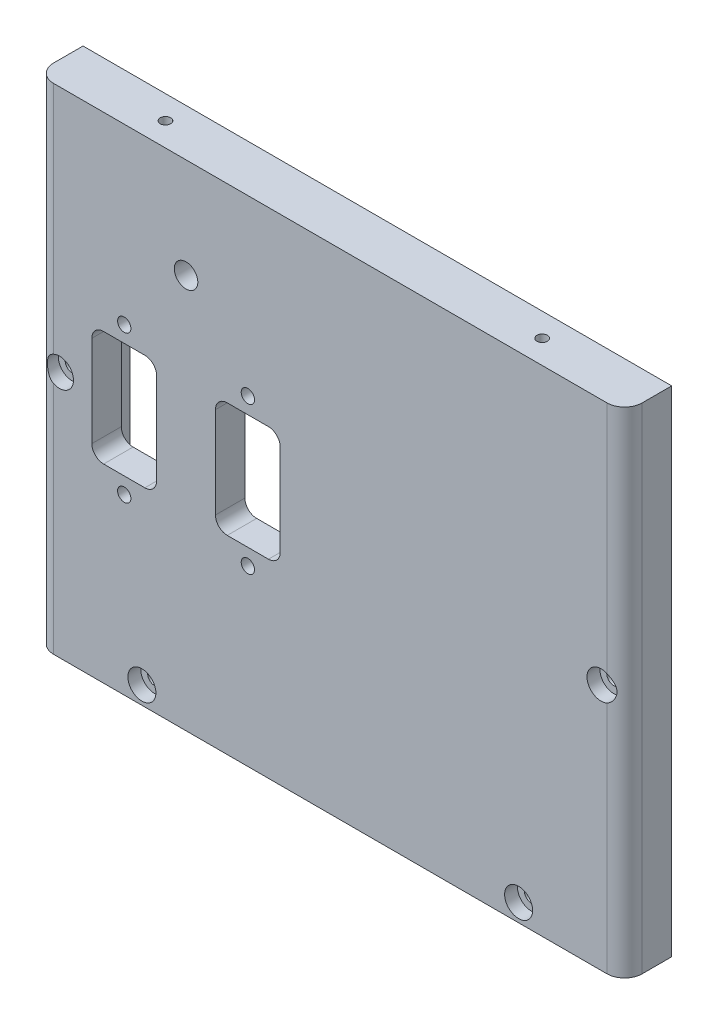
SolidWorks part; units mm, degrees
ref_plane "Front Plane" through (0, 0, 0) normal (0, 0, 1) x (1, 0, 0)
ref_plane "Top Plane" through (0, 0, 0) normal (0, 1, 0) x (1, 0, 0)
ref_plane "Right Plane" through (0, 0, 0) normal (1, 0, 0) x (0, 0, -1)
sketch "Sketch1" plane through (0, 0, 0) normal (0, 0, 1) x (1, 0, 0)
  line L1 (-50, 42) -> (50, 42)
  line L2 (-50, 42) -> (-50, -42)
  line L3 (-50, -42) -> (50, -42)
  line L4 (50, 42) -> (50, -42)
  line L5 (-50, 42) -> (50, -42) construction
  line L6 (-50, -42) -> (50, 42) construction
  point P0 (0, 0)
extrude "Boss-Extrude1" add sketch "Sketch1" along normal blind 8
sketch "Sketch2" plane through (0, 0, 8) normal (0, 0, 1) x (1, 0, 0)
  line L0 (-50, -42) -> (-50, -36) construction
  line L1 (-50, -36) -> (50, -36) construction
  line L2 (50, -42) -> (50, 42) construction
  line L3 (50, -36) -> (50, -42) construction
  line L4 (-50, -39) -> (-32, -39) construction
  line L5 (50, -39) -> (32, -39) construction
hole_wizard "CBORE for #2 Socket Head Cap Screw1" positions "3DSketch1" profile "Sketch3" counterbore size "#2" standard "ANSI Inch"
sketch3d "3DSketch1"
  point P0 (-32, -39, 8)
  point P3 (32, -39, 8)
sketch "Sketch3" plane through (-32, -39, 8) normal (1, 0, 0) x (0, -1, 0)
  line L0 (0, 0) -> (0, 13.0026)
  line L1 (0, 13.0026) -> (1.2192, 12.27)
  line L2 (1.2192, 12.27) -> (1.2192, 2.1844)
  line L3 (1.2192, 2.1844) -> (2.3812, 2.1844)
  line L4 (2.3812, 2.1844) -> (2.3812, 0)
  line L5 (2.3812, 0) -> (0, 0)
  line L10 (0, 13.0026) -> (-1.2192, 12.27) construction
  line L11 (0, -6.35) -> (0, 107.95) construction
  dimension "Hole Dia." = 2.4384
  dimension "Hole Depth" = 12.27
  dimension "C'Bore Dia." = 4.7625
  dimension "C'Bore Depth" = 2.1844
  dimension "Drill Angle" = 118
sketch "Sketch4" plane through (0, 0, 8) normal (0, 0, 1) x (1, 0, 0)
  line L0 (-50, -42) -> (-42, -42) construction
  line L1 (-42, -42) -> (-42, 42) construction
  line L2 (50, 42) -> (-50, 42) construction
  line L3 (-42, 42) -> (-50, 42) construction
  line L4 (50, -42) -> (42, -42) construction
  line L5 (42, -42) -> (42, 42) construction
  line L6 (42, 42) -> (50, 42) construction
  line L7 (46, -42) -> (46, 0) construction
  line L8 (-46, -42) -> (-46, 0) construction
hole_wizard "CBORE for #2 Socket Head Cap Screw2" positions "3DSketch2" profile "Sketch5" counterbore size "#2" standard "ANSI Inch"
sketch3d "3DSketch2"
  point P0 (-46, 0, 8)
  point P3 (46, 0, 8)
sketch "Sketch5" plane through (-46, 0, 8) normal (1, 0, 0) x (0, -1, 0)
  line L0 (0, 0) -> (0, 13.0026)
  line L1 (0, 13.0026) -> (1.2192, 12.27)
  line L2 (1.2192, 12.27) -> (1.2192, 2.1844)
  line L3 (1.2192, 2.1844) -> (2.3812, 2.1844)
  line L4 (2.3812, 2.1844) -> (2.3812, 0)
  line L5 (2.3812, 0) -> (0, 0)
  line L10 (0, 13.0026) -> (-1.2192, 12.27) construction
  line L11 (0, -6.35) -> (0, 107.95) construction
  dimension "Hole Dia." = 2.4384
  dimension "Hole Depth" = 12.27
  dimension "C'Bore Dia." = 4.7625
  dimension "C'Bore Depth" = 2.1844
  dimension "Drill Angle" = 118
sketch "Sketch6" plane through (0, 42, 0) normal (0, 1, 0) x (1, 0, 0)
  line L0 (-50, -4) -> (-32, -4) construction
  line L1 (-50, -8) -> (-50, 0) construction
  line L2 (50, -4) -> (32, -4) construction
  line L3 (50, -8) -> (50, 0) construction
hole_wizard "#2-56 Tapped Hole1" positions "3DSketch3" profile "Sketch7" tap size "#2-56" standard "ANSI Inch"
sketch3d "3DSketch3"
  point P0 (-32, 42, 4)
  point P3 (32, 42, 4)
sketch "Sketch7" plane through (-32, 42, 4) normal (1, 0, 0) x (0, 0, 1)
  line L0 (0, 0) -> (0, 12.5342)
  line L1 (0, 12.5342) -> (0.889, 12)
  line L2 (0.889, 12) -> (0.889, 0)
  line L5 (0.889, 0) -> (0, 0)
  line L10 (0, 12.5342) -> (-0.889, 12) construction
  line L11 (0, -6.35) -> (0, 107.95) construction
  dimension "Tap Drill Dia." = 1.778
  dimension "Tap Drill Depth" = 12
  dimension "Drill Angle" = 118
cosmetic thread "Hole Thread1" parameters "D1"=10, "D2"=2.1844
cosmetic thread "Hole Thread2" parameters "D1"=10, "D2"=2.1844
sketch "Sketch8" plane through (0, 0, 0) normal (0, 0, -1) x (-1, 0, 0)
  line L0 (-50, -42) -> (-50, -30) construction
  line L1 (-50, -30) -> (50, -30) construction
  line L2 (50, 42) -> (50, -42) construction
  line L3 (50, -30) -> (50, -42) construction
sketch "Sketch9" plane through (0, 0, 0) normal (0, 0, -1) x (-1, 0, 0)
  line L0 (50, -42) -> (42, -42) construction
  line L1 (42, -42) -> (42, 42) construction
  line L2 (-50, 42) -> (50, 42) construction
  line L3 (-50, -42) -> (-42, -42) construction
  line L4 (-42, -42) -> (-42, 42) construction
  line L5 (-50, 42) -> (-32, 42) construction
sketch "Sketch10" plane through (0, 0, 0) normal (0, 0, -1) x (-1, 0, 0)
  line L0 (-42, -42) -> (-37, -42) construction
  line L1 (-37, -42) -> (-37, 42) construction
  line L2 (-50, 42) -> (50, 42) construction
  line L3 (-37, -42) -> (-27, -42) construction
  line L4 (-27, -42) -> (-27, 42) construction
  line L5 (-27, -42) -> (3, -42) construction
  line L6 (3, -42) -> (3, 42) construction
  line L7 (3, -42) -> (7, -42) construction
  line L8 (7, -42) -> (7, 42) construction
sketch "Sketch12" plane through (0, 0, 0) normal (0, 0, -1) x (-1, 0, 0)
  line L0 (7, -42) -> (7, -30) construction
  line L1 (-50, -30) -> (50, -30) construction
  line L2 (7, -30) -> (42, -30) construction
  line L3 (42, -42) -> (42, 42) construction
  line L4 (42, -30) -> (42, 30) construction
  line L5 (42, 30) -> (7, 30) construction
  line L6 (7, -42) -> (7, 42) construction
  line L7 (7, 30) -> (7, -30) construction
  line L9 (7, 30) -> (42, 30)
  line L10 (7, 30) -> (7, -30)
  line L11 (7, -30) -> (42, -30)
  line L12 (42, 30) -> (42, -30)
extrude "Cut-Extrude3" cut sketch "Sketch12" against normal blind 3
fillet "Fillet1" radius 2 1 edges at (-7, 30, 1.5)
fillet "Fillet2" radius 2 1 edges at (-42, 30, 1.5)
fillet "Fillet3" radius 2 1 edges at (-42, -30, 1.5)
fillet "Fillet4" radius 2 1 edges at (-7, -30, 1.5)
sketch "Sketch13" plane through (0, 0, 3) normal (0, 0, -1) x (-1, 0, 0)
  line L0 (40, -30) -> (9, -30) construction
  line L1 (9, -30) -> (24.5, 0) construction
  line L2 (24.5, 0) -> (40, -30) construction
  line L3 (24.5, 0) -> (42, 0) construction
  line L4 (42, -28) -> (42, 28) construction
sketch "Sketch14" plane through (0, 0, 3) normal (0, 0, -1) x (-1, 0, 0)
  line L0 (24.5, 0) -> (7, 0) construction
  line L1 (7, 28) -> (7, -28) construction
sketch "Sketch15" plane through (0, 0, 3) normal (0, 0, -1) x (-1, 0, 0)
  line L0 (24.5, 0) -> (29.5, 0) construction
  line L1 (24.5, 0) -> (19.5, 0) construction
  line L2 (29.5, 0) -> (40.5, 0) construction
  line L3 (40.5, 0) -> (40.5, 9.75) construction
sketch "Sketch16" plane through (0, 0, 3) normal (0, 0, -1) x (-1, 0, 0)
  line L0 (19.5, 0) -> (8.5, 0) construction
  line L1 (19.5, 0) -> (19.5, -9.75) construction
  line L2 (8.5, 0) -> (8.5, 9.75) construction
  line L3 (29.5, 0) -> (29.5, -9.75) construction
  line L4 (8.5, 9.75) -> (19.5, 9.75)
  line L5 (8.5, 9.75) -> (8.5, -9.75)
  line L6 (8.5, -9.75) -> (19.5, -9.75)
  line L7 (19.5, 9.75) -> (19.5, -9.75)
sketch "Sketch17" plane through (0, 0, 3) normal (0, 0, -1) x (-1, 0, 0)
  line L1 (29.5, -9.75) -> (40.5, -9.75)
  line L2 (29.5, -9.75) -> (29.5, 9.75)
  line L3 (29.5, 9.75) -> (40.5, 9.75)
  line L4 (40.5, -9.75) -> (40.5, 9.75)
extrude "Cut-Extrude4" cut sketch "Sketch17" against normal blind 8 contours L2 L1 L4 L3
extrude "Cut-Extrude5" cut sketch "Sketch16" against normal blind 8
fillet "Fillet5" radius 2 2 edges at (-40.5, 9.75, 5.5) (-19.5, 9.75, 5.5)
fillet "Fillet6" radius 2 2 edges at (-29.5, 9.75, 5.5) (-8.5, 9.75, 5.5)
fillet "Fillet7" radius 2 2 edges at (-29.5, -9.75, 5.5) (-8.5, -9.75, 5.5)
fillet "Fillet8" radius 2 2 edges at (-40.5, -9.75, 5.5) (-19.5, -9.75, 5.5)
sketch "Sketch19" plane through (0, 0, 8) normal (0, 0, 1) x (1, 0, 0)
  line L0 (-38.5, 9.75) -> (-31.5, 9.75) construction
  line L1 (-38.5, 9.75) -> (-31.5, 9.75) construction
  line L4 (-38.5, 12.5) -> (-38.5, 9.75) construction
  line L5 (-38.5, 12.5) -> (-35, 12.5) construction
  line L6 (-35, 12.5) -> (-35, 9.75) construction
  line L7 (-17.5, 9.75) -> (-10.5, 9.75) construction
  line L8 (-10.5, 9.75) -> (-10.5, 12.5) construction
  line L9 (-10.5, 12.5) -> (-14, 12.5) construction
  line L10 (-14, 12.5) -> (-14, 9.75) construction
  line L11 (-10.5, -9.75) -> (-17.5, -9.75) construction
  line L15 (-10.5, -9.75) -> (-14, -9.75) construction
  line L16 (-14, -9.75) -> (-14, -12.5) construction
  line L17 (-38.5, -9.75) -> (-31.5, -9.75) construction
  line L18 (-31.5, -9.75) -> (-31.5, -12.5) construction
  line L19 (-31.5, -12.5) -> (-35, -12.5) construction
  line L20 (-35, -12.5) -> (-35, -9.75) construction
  arc A0 (-29.5, 7.75) -> (-31.5, 9.75) centre (-31.5, 7.75) ccw construction
hole_wizard "#4-40 Tapped Hole1" positions "3DSketch4" profile "Sketch20" tap size "#4-40" standard "ANSI Inch" end condition through all
sketch3d "3DSketch4"
  point P0 (-35, 12.5, 8)
  point P3 (-35, -12.5, 8)
  point P6 (-14, -12.5, 8)
  point P9 (-14, 12.5, 8)
sketch "Sketch20" plane through (-35, 12.5, 8) normal (1, 0, 0) x (0, -1, 0)
  line L0 (0, 0) -> (0, 8)
  line L1 (0, 8) -> (1.1303, 8)
  line L2 (1.1303, 8) -> (1.1303, 0)
  line L5 (1.1303, 0) -> (0, 0)
  line L11 (0, -6.35) -> (0, 107.95) construction
  dimension "Thru Tap Drill Dia." = 2.2606
  dimension "Thru Tap Drill Depth" = 8
cosmetic thread "Hole Thread3" parameters "D2"=2.8448
cosmetic thread "Hole Thread4" parameters "D2"=2.8448
cosmetic thread "Hole Thread5" parameters "D2"=2.8448
cosmetic thread "Hole Thread6" parameters "D2"=2.8448
sketch "Sketch21" plane through (0, 0, 3) normal (0, 0, -1) x (-1, 0, 0)
  line L0 (24.5, 0) -> (24.5, 25) construction
  circle A0 centre (24.5, 25) radius 2
extrude "Cut-Extrude6" cut sketch "Sketch21" against normal blind 8
fillet "Fillet9" radius 3 2 edges at (50, 0, 8) (-50, 0, 8)
